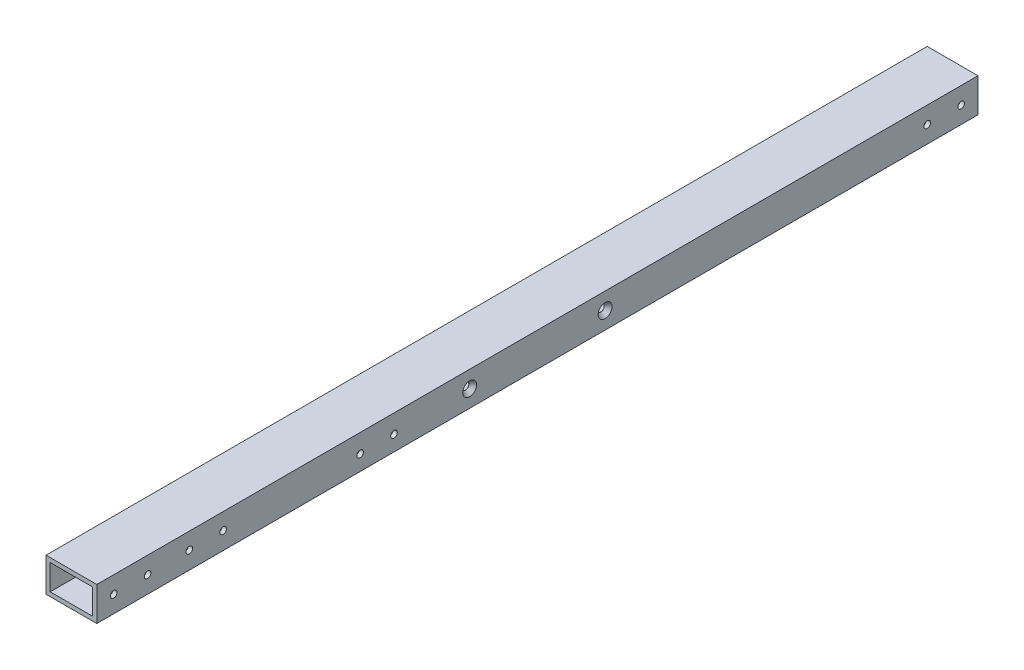
SolidWorks part; units mm, degrees
ref_plane "Front Plane" through (0, 0, 0) normal (0, 0, 1) x (1, 0, 0)
ref_plane "Top Plane" through (0, 0, 0) normal (0, 1, 0) x (1, 0, 0)
ref_plane "Right Plane" through (0, 0, 0) normal (1, 0, 0) x (0, 0, -1)
sketch "Sketch1" plane through (0, 0, 0) normal (0, 0, 1) x (1, 0, 0)
  line L0 (-15.875, 9.525) -> (15.875, 9.525)
  line L2 (-19.05, 12.7) -> (19.05, 12.7)
  line L3 (-19.05, 12.7) -> (-19.05, -12.7)
  line L4 (-19.05, -12.7) -> (19.05, -12.7)
  line L5 (19.05, 12.7) -> (19.05, -12.7)
  line L10 (15.875, 9.525) -> (15.875, -9.525)
  line L11 (-15.875, -9.525) -> (15.875, -9.525)
  line L12 (-15.875, 9.525) -> (-15.875, -9.525)
  point P12 (0, 12.7)
  point P14 (19.05, 0)
  dimension "Wall Thickness" = 3.175
  dimension "Outside Width" = 38.1
  dimension "Outside Height" = 25.4
  dimension "Inside Height" = 19.05
  dimension "Inside Width" = 31.75
sketch "Sketch2" plane through (0, 0, 0) normal (1, 0, 0) x (0, 0, -1)
  line L0 (330.5556, 0) -> (-330.5556, 0)
  point P4 (0, 0)
  point P7 (-330.5556, 0)
  point P10 (330.5556, 0)
  dimension "Length" = 661.1112
sketch "Sketch3" plane through (0, 0, 0) normal (0, 0, 1) x (1, 0, 0)
  line L21 (19.05, 12.7) -> (-19.05, 12.7)
  line L22 (19.05, -12.7) -> (19.05, 12.7)
  line L23 (-19.05, -12.7) -> (19.05, -12.7)
  line L24 (-19.05, 12.7) -> (-19.05, -12.7)
  line L25 (19.05, 12.7) -> (-19.05, 12.7)
  line L26 (19.05, -12.7) -> (19.05, 12.7)
  line L27 (-19.05, -12.7) -> (19.05, -12.7)
  line L28 (-19.05, 12.7) -> (-19.05, -12.7)
  line L29 (15.875, 9.525) -> (-15.875, 9.525)
  line L30 (15.875, -9.525) -> (15.875, 9.525)
  line L31 (-15.875, -9.525) -> (15.875, -9.525)
  line L32 (-15.875, 9.525) -> (-15.875, -9.525)
  line L33 (15.875, 9.525) -> (-15.875, 9.525)
  line L34 (15.875, -9.525) -> (15.875, 9.525)
  line L35 (-15.875, -9.525) -> (15.875, -9.525)
  line L36 (-15.875, 9.525) -> (-15.875, -9.525)
  dimension "D1" = 0
  dimension "D2" = 0
extrude "Boss-Extrude1" add sketch "Sketch3" along normal up to vertex (330.5556 mm away) and the other way up to vertex (330.5556 mm away) up to point (0, 0, 330.5556) other way up to point (0, 0, -330.5556)
sketch "Drawing Reference" plane through (0, 0, 0) normal (1, 0, 0) x (0, 0, -1)
  line L0 (-330.5556, 0) -> (330.5556, 0) construction
  line L1 (0, -12.7) -> (0, 12.7) construction
  line L2 (-330.5556, -12.7) -> (330.5556, -12.7) construction
  line L5 (-330.5556, 12.7) -> (330.5556, 12.7) construction
  point P7 (-303.1236, 0)
  point P8 (303.1236, 0)
  dimension "D1" = 27.432
sketch "Sketch4" plane through (-19.05, 0, 0) normal (-1, 0, 0) x (0, 0, 1)
  line L0 (-330.5556, 0) -> (-317.8556, 0)
  line L1 (-330.5556, 12.7) -> (-330.5556, -12.7) construction
  line L2 (-317.8556, 0) -> (-292.4556, 0)
  line L3 (330.5556, 12.7) -> (330.5556, -12.7) construction
  line L4 (330.5556, 0) -> (317.8556, 0)
  line L5 (317.8556, 0) -> (292.4556, 0)
  line L6 (0, 0) -> (50.8, 0) construction
  line L7 (0, 0) -> (-50.8, 0) construction
  point P11 (-317.8556, 0)
  point P13 (-292.4556, 0)
  point P14 (317.8556, 0)
  point P15 (292.4556, 0)
hole_wizard "#10 Clearance Hole2" positions "Sketch11" profile "Sketch12" hole size "#10" standard "ANSI Inch" end condition through all
sketch "Sketch11" plane through (-19.05, 0, 0) normal (-1, 0, 0) x (0, 0, 1)
  point P0 (-317.8556, 0)
  point P3 (-292.4556, 0)
  point P6 (292.4556, 0)
  point P9 (317.8556, 0)
sketch "Sketch12" plane through (-19.05, 0, -317.8556) normal (0, 1, 0) x (0, 0, 1)
  line L0 (0, 0) -> (0, 38.1)
  line L1 (0, 38.1) -> (2.4892, 38.1)
  line L2 (2.4892, 38.1) -> (2.4892, 0)
  line L5 (2.4892, 0) -> (0, 0)
  line L11 (0, -6.35) -> (0, 107.95) construction
  dimension "Thru Hole Dia." = 4.9784
  dimension "Thru Hole Depth" = 38.1
hole_wizard "#10 Clearance Hole5" positions "Sketch14" profile "Sketch16" hole size "#10" standard "ANSI Inch" end condition through all
sketch "Sketch14" plane through (19.05, 0, 0) normal (1, 0, 0) x (0, 0, -1)
  point P10 (-132.9849, -1.2316)
  point P13 (-107.5849, -1.2316)
  point P17 (-261.1289, 0.3559)
  point P20 (-235.7289, 0.3559)
sketch "Sketch16" plane through (19.05, -1.2316, 132.9849) normal (0, 1, 0) x (0, 0, -1)
  line L0 (0, 0) -> (0, 38.1)
  line L1 (0, 38.1) -> (2.4892, 38.1)
  line L2 (2.4892, 38.1) -> (2.4892, 0)
  line L5 (2.4892, 0) -> (0, 0)
  line L11 (0, -6.35) -> (0, 107.95) construction
  dimension "Thru Hole Dia." = 4.9784
  dimension "Thru Hole Depth" = 38.1
sketch "Sketch17" plane through (19.05, 0, 0) normal (1, 0, 0) x (0, 0, -1)
  point P0 (-261.1289, 0.3559)
  point P1 (-235.7289, 0.3559)
hole_wizard "#10 Clearance Hole4" positions "Sketch18" profile "Sketch19" hole size "#10" standard "ANSI Inch" end condition through all
sketch "Sketch18" plane through (19.05, 0, 0) normal (1, 0, 0) x (0, 0, -1)
  point P0 (-261.1289, 0.3559)
  point P3 (-235.7289, 0.3559)
sketch "Sketch19" plane through (19.05, 0.3559, 261.1289) normal (0, 1, 0) x (0, 0, -1)
  line L0 (0, 0) -> (0, 38.1)
  line L1 (0, 38.1) -> (2.4892, 38.1)
  line L2 (2.4892, 38.1) -> (2.4892, 0)
  line L5 (2.4892, 0) -> (0, 0)
  line L11 (0, -6.35) -> (0, 107.95) construction
  dimension "Thru Hole Dia." = 4.9784
  dimension "Thru Hole Depth" = 38.1
hole_wizard "#10 Clearance Hole3" positions "Sketch20" profile "Sketch21" hole size "#10" standard "ANSI Inch" end condition through all
sketch "Sketch20" plane through (-19.05, 0, 0) normal (-1, 0, 0) x (0, 0, 1)
  point P0 (-50.8, 0)
  point P3 (50.8, 0)
sketch "Sketch21" plane through (-19.05, 0, -50.8) normal (0, 1, 0) x (0, 0, 1)
  line L0 (0, 0) -> (0, 38.1)
  line L1 (0, 38.1) -> (5.207, 38.1)
  line L2 (2.4892, 34.9735) -> (2.4892, 0)
  line L5 (2.4892, 0) -> (0, 0)
  line L7 (5.207, 38.1) -> (2.4892, 34.9735)
  line L8 (-5.207, 38.1) -> (-2.4892, 34.9735) construction
  line L11 (0, -6.35) -> (0, 107.95) construction
  dimension "Thru Hole Dia." = 4.9784
  dimension "Thru Hole Depth" = 38.1
  dimension "Far C'Sink Dia." = 10.414
  dimension "Far C'Sink Angle" = 82
equation "\"D1@Drawing Reference\"=\"Outside Width@Sketch1\" * 0.72"
